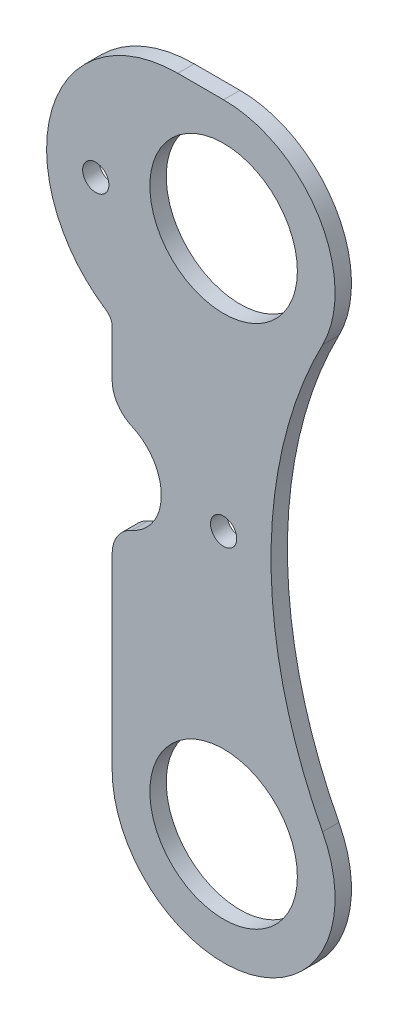
SolidWorks part; units mm, degrees
material "6061 Alloy"
ref_plane "Front Plane" through (0, 0, 0) normal (0, 0, 1) x (1, 0, 0)
ref_plane "Top Plane" through (0, 0, 0) normal (0, 1, 0) x (1, 0, 0)
ref_plane "Right Plane" through (0, 0, 0) normal (1, 0, 0) x (0, 0, -1)
sketch "Sketch1" plane through (0, 0, 0) normal (0, 0, 1) x (1, 0, 0)
  line L0 (0, 0) -> (0, -101.6) construction
  line L1 (21.59, -120.5575) -> (-21.59, -120.5575) construction
  line L2 (-8.89, 25.4) -> (8.89, 25.4)
  line L3 (-21.59, 12.7) -> (-21.59, -117.7751)
  line L5 (21.59, 12.7) -> (21.59, -117.7751)
  line L9 (-23.3829, -122.6853) -> (-33.2033, -134.3394)
  line L10 (-36.322, 25.4) -> (20.828, 25.4) construction
  line L11 (-36.322, 25.4) -> (-36.322, -203.2) construction
  line L12 (-36.322, -203.2) -> (20.828, -203.2) construction
  line L13 (20.828, 25.4) -> (20.828, -203.2) construction
  line L15 (-7.9527, -155.6168) -> (19.7971, -122.6853)
  line L16 (-32.4392, -143.2871) -> (-16.9004, -156.3809)
  circle A0 centre (0, 0) radius 38.1 construction
  circle A1 centre (0, -101.6) radius 38.1 construction
  circle A2 centre (0, 0) radius 14.2875
  circle A3 centre (0, -101.6) radius 14.2875
  arc A6 (8.89, 25.4) -> (21.59, 12.7) centre (8.89, 12.7) cw
  arc A7 (-8.89, 25.4) -> (-21.59, 12.7) centre (-8.89, 12.7) ccw
  circle A10 centre (-18.5321, -142.5501) radius 2.54
  arc A13 (-23.3829, -122.6853) -> (-21.59, -117.7751) centre (-29.21, -117.7751) ccw
  arc A14 (19.7971, -122.6853) -> (21.59, -117.7751) centre (13.97, -117.7751) ccw
  arc A15 (-16.9004, -156.3809) -> (-7.9527, -155.6168) centre (-12.8086, -151.525) ccw
  arc A16 (-33.2033, -134.3394) -> (-32.4392, -143.2871) centre (-28.3474, -138.4312) ccw
  circle A17 centre (0, -50.8) radius 2.54
  point P13 (-192.705, 39.2708)
  point P20 (21.59, 25.4)
  point P23 (-21.59, 25.4)
  point P27 (0, 0)
  point P29 (0, 0)
  point P31 (-36.322, -138.0404)
  dimension "D2" = 76.2
  dimension "D3" = 76.2
  dimension "D4" = 28.575
  dimension "D5" = 28.575
  dimension "D10" = 228.6
  dimension "D11" = 36.322
  dimension "D13" = 5.08
  dimension "D19" = 6.35
  dimension "D20" = 7.62
  dimension "D21" = 12.7
  dimension "D22" = 5.08
  dimension "D1" = 101.6
  dimension "D6" = 43.18
  dimension "D7" = 21.59
  dimension "D8" = 25.4
  dimension "D9" = 57.15
  dimension "D12" = 25.4
  dimension "D14" = 33.02
  dimension "D15" = 16.51
  dimension "D16" = 21.59
  dimension "D17" = 9.525
  dimension "D18" = 18.9575
extrude "Boss-Extrude1" add sketch "Sketch1" along normal blind 3.175
sketch "Sketch2" plane through (0, 0, 0) normal (0, 0, 1) x (1, 0, 0)
  line L0 (-21.59, -41.275) -> (-21.59, -60.325)
  line L1 (0, 0) -> (0, -101.6) construction
  line L4 (21.59, -117.7751) -> (21.59, 12.7) construction
  line L5 (-21.59, -50.8) -> (97.79, -50.8) construction
  line L6 (-21.59, 12.7) -> (-21.59, -117.7751) construction
  line L7 (0, 0) -> (-39.9512, 0) construction
  line L9 (16.51, -115.5122) -> (-17.5013, -155.8745)
  line L10 (-32.4392, -143.2871) -> (-16.9004, -156.3809) construction
  line L11 (-7.9527, -155.6168) -> (19.7971, -122.6853) construction
  line L13 (27.94, -121.6567) -> (-7.6203, -163.8572)
  line L14 (-7.6203, -163.8572) -> (-17.5013, -155.8745)
  line L15 (27.94, -121.6567) -> (27.94, 0)
  line L16 (27.94, 0) -> (21.59, 0)
  arc A1 (19.1591, -91.6472) -> (19.1591, -9.9528) centre (97.79, -50.8) cw
  arc A2 (-21.59, -60.325) -> (-21.59, -41.275) centre (-21.59, -50.8) ccw
  arc A3 (21.59, 0) -> (19.1591, -9.9528) centre (0, 0) cw
  arc A4 (21.59, -101.6) -> (19.1591, -91.6472) centre (0, -101.6) ccw
  arc A5 (21.59, -101.6) -> (16.51, -115.5122) centre (0, -101.6) cw
  dimension "D2" = 12.7
  dimension "D3" = 50.8
  dimension "D4" = 6.35
  dimension "D1" = 76.2
  dimension "D5" = 19.05
extrude "Cut-Extrude1" cut sketch "Sketch2" along normal through all contours A1 A3 L16 L15 L13 L14 L9 A5 A4 | L0 A2
sketch "Sketch3" plane through (0, 0, 3.175) normal (0, 0, 1) x (1, 0, 0)
  line L0 (-27.3514, -127.3948) -> (-36.0255, -137.6886)
  line L3 (-27.3514, -127.3948) -> (-7.5576, -144.074)
  line L4 (-23.3829, -122.6853) -> (-33.2033, -134.3394) construction
  line L5 (16.51, -115.5122) -> (-17.5013, -155.8745) construction
  line L7 (-35.4064, -144.9387) -> (-24.4031, -154.2106)
  line L8 (-23.3829, -122.6853) -> (-33.2033, -134.3394) construction
  line L9 (-7.5576, -144.074) -> (-15.4554, -153.4465)
  line L10 (-32.4392, -143.2871) -> (-17.5013, -155.8745) construction
  circle A2 centre (-18.5321, -142.5501) radius 2.54
  circle A3 centre (-18.5321, -142.5501) radius 2.54 construction
  arc A5 (-36.0255, -137.6886) -> (-35.4064, -144.9387) centre (-32.0909, -141.0041) ccw
  arc A6 (-24.4031, -154.2106) -> (-15.4554, -153.4465) centre (-20.3113, -149.3547) ccw
  dimension "D2" = 6.35
  dimension "D3" = 5.1453
  dimension "D1" = 3.175
fillet "Fillet3" radius 6.35 2 edges at (-21.59, -41.275, 1.5875) (-21.59, -60.325, 1.5875)
extrude "Boss-Extrude3" add sketch "Sketch3" against normal blind 3.175
sketch "Sketch6" plane through (0, 0, 3.175) normal (0, 0, 1) x (1, 0, 0)
  line L0 (-35.4064, -144.9387) -> (-63.6204, -121.1641)
  line L1 (-63.6204, -121.1641) -> (-51.345, -106.5965)
  line L2 (-51.345, -106.5965) -> (-27.0656, -127.0555)
  line L4 (-35.4064, -144.9387) -> (-24.4031, -154.2106) construction
  line L5 (-23.3829, -122.6853) -> (-36.0255, -137.6886) construction
  line L6 (-35.4064, -144.9387) -> (-27.0656, -127.0555)
  circle A0 centre (-52.6268, -117.9721) radius 2.54
  dimension "D4" = 5.08
  dimension "D1" = 31.75
  dimension "D2" = 9.525
  dimension "1" = 19.05
  dimension "D3" = 6.35
extrude "Boss-Extrude4" add sketch "Sketch6" against normal blind 3.175
fillet "Fillet2" radius 6.35 3 edges at (-63.6204, -121.1641, 1.5875) (-51.345, -106.5965, 1.5875) (-27.0656, -127.0555, 1.5875)
sketch "Sketch7" plane through (0, 0, 3.175) normal (0, 0, 1) x (1, 0, 0)
  line L0 (-21.59, 12.7) -> (-21.59, -36.2503) construction
  line L1 (21.59, 0) -> (21.59, 12.7) construction
  line L2 (-21.59, 0) -> (21.59, 0) construction
  line L3 (-21.59, 0) -> (-21.59, 31.75)
  line L4 (-21.59, 31.75) -> (21.59, 31.75)
  line L5 (21.59, 31.75) -> (21.59, 0)
  line L6 (8.89, 25.4) -> (-8.89, 25.4) construction
  arc A0 (-21.59, 0) -> (21.59, 0) centre (0, 0) cw
  dimension "D1" = 6.35
extrude "Cut-Extrude2" cut sketch "Sketch7" against normal through all
sketch "Sketch10" plane through (0, 0, 3.175) normal (0, 0, 1) x (1, 0, 0)
  line L0 (16.51, -115.5122) -> (-17.5013, -155.8745) construction
  line L1 (-18.1519, -155.3263) -> (-17.3615, -157.512)
  line L2 (-17.3615, -157.512) -> (-14.3757, -156.4323)
  line L3 (-14.3757, -156.4323) -> (-15.4554, -153.4465)
  line L5 (-18.1519, -155.3263) -> (-17.5013, -155.8745) construction
  circle A0 centre (-20.3113, -149.3547) radius 6.35 construction
  arc A1 (-24.4031, -154.2106) -> (-18.1519, -155.3263) centre (-20.3113, -149.3547) ccw construction
  arc A2 (-18.1519, -155.3263) -> (-15.4554, -153.4465) centre (-20.3113, -149.3547) ccw
  dimension "D1" = 3.175
  dimension "D2" = 30
extrude "Cut-Extrude3" cut sketch "Sketch10" against normal through all
sketch "Sketch12" plane through (0, 0, 3.175) normal (0, 0, 1) x (1, 0, 0)
  line L0 (-21.59, -65.3497) -> (-21.59, -117.7751) construction
  line L1 (-21.59, -101.6) -> (-72.39, -101.6)
  line L2 (-72.39, -101.6) -> (-72.39, -165.1)
  line L3 (-72.39, -165.1) -> (16.51, -165.1)
  line L4 (16.51, -165.1) -> (16.51, -115.5122)
  arc A2 (16.51, -115.5122) -> (-21.59, -101.6) centre (0, -101.6) cw
  dimension "D1" = 63.5
  dimension "D2" = 88.9
extrude "Cut-Extrude4" cut sketch "Sketch12" against normal through all
sketch "Sketch15" plane through (0, 0, 3.175) normal (0, 0, 1) x (1, 0, 0)
  line L0 (-21.59, 0) -> (-21.59, -36.2503) construction
  line L5 (-21.59, -29.21) -> (-21.59, 0)
  line L7 (0, 21.59) -> (-16.6076, 6.9565)
  line L8 (-16.6076, 6.9565) -> (-12.5785, -28.9408)
  line L9 (-8.89, 21.59) -> (0, 21.59)
  arc A0 (-12.5785, -28.9408) -> (-34.29, -3.81) centre (-8.89, -3.81) cw
  arc A1 (-8.89, 21.59) -> (-34.29, -3.81) centre (-8.89, -3.81) ccw
  circle A2 centre (-24.765, -3.81) radius 2.54
  arc A3 (19.1591, -9.9528) -> (-21.59, 0) centre (0, 0) ccw construction
  arc M10 (19.1591, -9.9528) -> (-21.59, 0) centre (0, 0) ccw
  line M11 (-21.59, 0) -> (-21.59, -36.2503)
  dimension "D1" = 12.7
  dimension "D4" = 3.175
  dimension "D3" = 5.08
  dimension "D2" = 25.4
extrude "Boss-Extrude8" add sketch "Sketch15" against normal blind 3.175 contours L9 A1 A0 A2 M11 M10 region at (-24.9677, -0.0937, 3.175)
fillet "Fillet4" radius 2.54 1 edges at (-21.59, -25.807, 1.5875)
